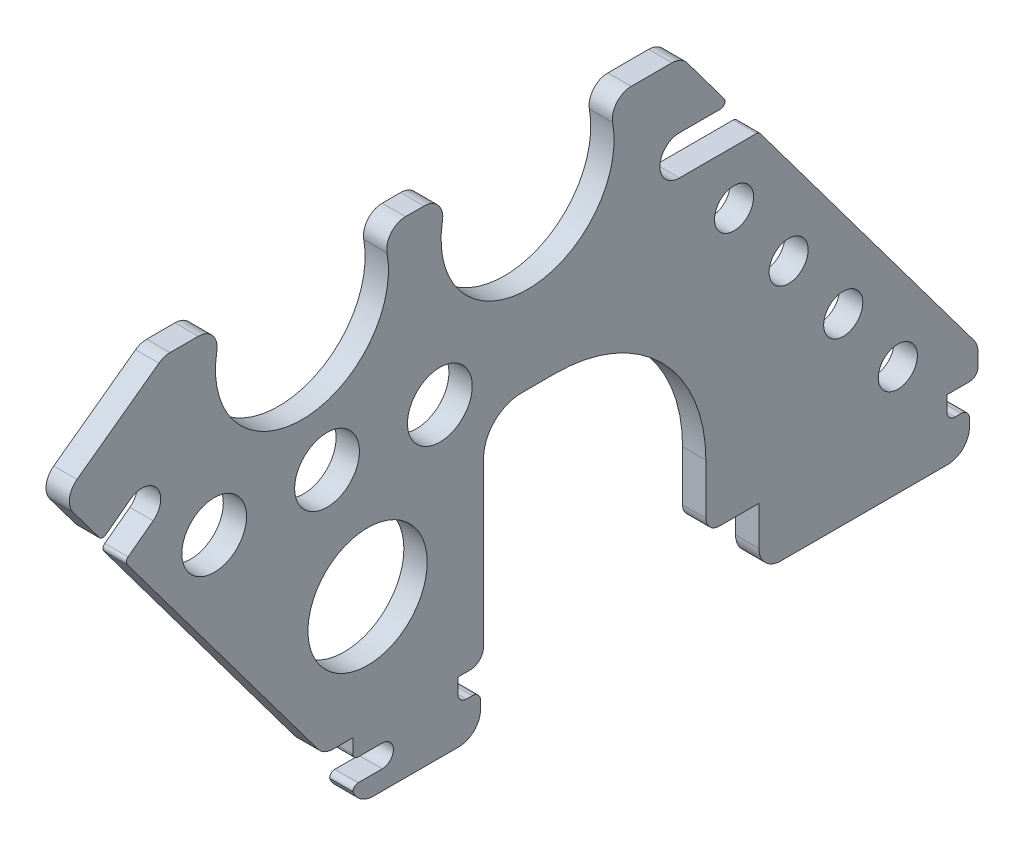
SolidWorks part; units mm, degrees
ref_plane "Front Plane" through (0, 0, 0) normal (0, 0, 1) x (1, 0, 0)
ref_plane "Top Plane" through (0, 0, 0) normal (0, 1, 0) x (1, 0, 0)
ref_plane "Right Plane" through (0, 0, 0) normal (1, 0, 0) x (0, 0, -1)
sketch "Sketch1" plane through (0, 0, 0) normal (1, 0, 0) x (0, 0, -1)
  line L0 (0, 0) -> (0, -3.1)
  line L1 (0, -3.1) -> (3, -3.1)
  line L2 (3, -3.1) -> (3, -8.1)
  line L3 (3, -8.1) -> (-25, -8.1)
  line L4 (-25, -8.1) -> (-25, 0)
  line L5 (-25, 0) -> (-65, 0)
  line L6 (-65, 0) -> (-65, -3.1)
  line L7 (-104.1118, 56.5) -> (-117.7038, 46.5901)
  line L8 (-78.9797, -8.1) -> (-78.9797, 0)
  line L9 (-117.7038, 46.5901) -> (-82.8802, 0)
  line L10 (-104.1118, 56.5) -> (-96.1118, 56.5)
  line L11 (0, 0) -> (4.13, 0)
  line L12 (-85.7556, 51.5) -> (-55.7556, 51.5) construction
  line L13 (-85.7556, 40) -> (-55.7556, 40) construction
  line L14 (-75.3994, 56.5) -> (-66.1118, 56.5)
  line L15 (-65, -3.1) -> (-62, -3.1)
  line L16 (-62, -3.1) -> (-62, -8.1)
  line L17 (-62, -8.1) -> (-78.9797, -8.1)
  line L18 (-82.8802, 0) -> (-78.9797, 0)
  line L19 (-45.3994, 56.5) -> (-35.2992, 56.5)
  line L20 (-35.2992, 56.5) -> (4.13, 3.7482)
  line L21 (4.13, 3.7482) -> (4.13, 0)
  arc A0 (-96.1118, 56.5) -> (-75.3994, 56.5) centre (-85.7556, 51.5) ccw
  arc A1 (-66.1118, 56.5) -> (-45.3994, 56.5) centre (-55.7556, 51.5) ccw
  point P27 (-112.3367, 58)
  point P28 (0, 0)
  point P29 (-72.7383, 51.5)
  point P30 (-74.8611, 51.5)
  point P31 (-71.1944, 51.5)
  point P32 (-35.2992, 56.5)
  point P33 (-55.7556, 51.5)
  point P34 (-117.7038, 46.5901)
  dimension "D1" = 23
  dimension "D2" = 65
  dimension "D3" = 5
  dimension "D4" = 40
  dimension "D5" = 30
  dimension "D6" = 25
  dimension "D7" = 3
  dimension "D8" = 8
  dimension "D9" = 3.1
  dimension "D10" = 5
extrude "Boss-Extrude1" add sketch "Sketch1" along normal blind 3.1
fillet "Fillet1" radius 2.5 9 edges at (1.55, 56.5, 66.1118) (1.55, 56.5, 75.3994) (1.55, 56.5, 96.1118) (1.55, 0, 82.8802) (1.55, 3.7482, -4.13) (1.55, 56.5, 35.2992) (1.55, 46.5901, 117.7038) (1.55, 56.5, 104.1118) (1.55, 56.5, 45.3994)
fillet "Fillet2" radius 1.1 1 edges at (1.55, 0, -4.13)
sketch "Sketch2" plane through (3.1, 0, 0) normal (1, 0, 0) x (0, 0, -1)
  line L0 (-78.9797, -4.05) -> (-75.0799, -4.05) construction
  line L1 (-78.9797, 0) -> (-78.9797, -8.1) construction
  line L2 (-78.9797, -2.5672) -> (-75.0799, -2.5672)
  line L3 (-78.9797, -5.5328) -> (-75.0799, -5.5328)
  line L5 (-65, 0) -> (-25, 0) construction
  line L6 (-61.6078, 0) -> (-32.0503, 0)
  line L7 (-61.6078, 0) -> (-61.6078, 28.4851)
  line L8 (-61.6078, 28.4851) -> (-32.0503, 28.4851)
  line L9 (-32.0503, 0) -> (-32.0503, 28.4851)
  arc A0 (-78.9797, -2.5672) -> (-78.9797, -5.5328) centre (-78.9797, -4.05) ccw
  arc A1 (-75.0799, -5.5328) -> (-75.0799, -2.5672) centre (-75.0799, -4.05) ccw
  circle A2 centre (-97.4184, 32.5561) radius 4.3044
  circle A3 centre (-77.0298, 15.273) radius 7.9253
  circle A4 centre (-82.4184, 32.5561) radius 4.3044
  circle A6 centre (-67.4184, 32.5561) radius 4.3044
  point P4 (-77.0298, -4.05)
  point P21 (-67.4184, 32.5561)
  point P22 (-77.0298, 15.273)
  dimension "D1" = 3
extrude "Cut-Extrude1" cut sketch "Sketch2" against normal blind 4
fillet "Fillet3" radius 0.7 2 edges at (1.55, -2.5672, 78.9797) (1.55, -5.5328, 78.9797)
fillet "Fillet4" radius 1.1 4 edges at (1.55, -3.1, -3) (1.55, -3.1, 0) (1.55, -3.1, 62) (1.55, -3.1, 65)
fillet "Fillet5" radius 2.9 4 edges at (1.55, -8.1, -3) (1.55, -8.1, 25) (1.55, -8.1, 62) (1.55, -8.1, 78.9797)
fillet "Fillet6" radius 20 1 edges at (1.55, 28.4851, 32.0503)
fillet "Fillet7" radius 5 1 edges at (1.55, 28.4851, 61.6078)
fillet "Fillet8" radius 1.8 2 edges at (1.55, 0, 32.0503) (1.55, 0, 61.6078)
sketch "Sketch4" plane through (3.1, 0, 0) normal (1, 0, 0) x (0, 0, -1)
  line L0 (-35.5622, 47.9422) -> (-28.9027, 47.9422)
  line L1 (-28.9027, 47.9422) -> (-25.016, 42.7422)
  line L2 (-25.016, 42.7422) -> (-35.5622, 42.7422)
  line L3 (-110.8437, 37.412) -> (-107.033, 40.2603) construction
  line L4 (-116.1892, 44.5637) -> (-83.6301, 1.0033) construction
  line L5 (-112.3405, 39.4145) -> (-108.5298, 42.2628)
  line L6 (-109.347, 35.4096) -> (-105.5363, 38.2579)
  line L7 (-35.5622, 45.3422) -> (-28.3037, 35.6313) construction
  line L8 (-28.3037, 35.6313) -> (-21.0453, 25.9203) construction
  line L9 (-21.0453, 25.9203) -> (-13.7869, 16.2094) construction
  line L10 (-13.7869, 16.2094) -> (-6.5284, 6.4984) construction
  line L11 (3.6325, 4.4138) -> (-34.5493, 55.4967) construction
  arc A0 (-35.5622, 47.9422) -> (-35.5622, 42.7422) centre (-35.5622, 45.3422) ccw
  circle A1 centre (-28.3037, 35.6313) radius 2.6
  circle A2 centre (-21.0453, 25.9203) radius 2.6
  circle A3 centre (-13.7869, 16.2094) radius 2.6
  circle A4 centre (-6.5284, 6.4984) radius 2.6
  arc A7 (-112.3405, 39.4145) -> (-109.347, 35.4096) centre (-110.8437, 37.412) ccw
  arc A8 (-105.5363, 38.2579) -> (-108.5298, 42.2628) centre (-107.033, 40.2603) ccw
  point P16 (-108.9384, 38.8362)
  dimension "D1" = 5.2
  dimension "D2" = 5
extrude "Cut-Extrude2" cut sketch "Sketch4" against normal through all
fillet "Fillet9" radius 0.6 4 edges at (1.55, 35.4096, 109.347) (1.55, 39.4145, 112.3405) (1.55, 42.7422, 25.016) (1.55, 47.9422, 28.9027)
